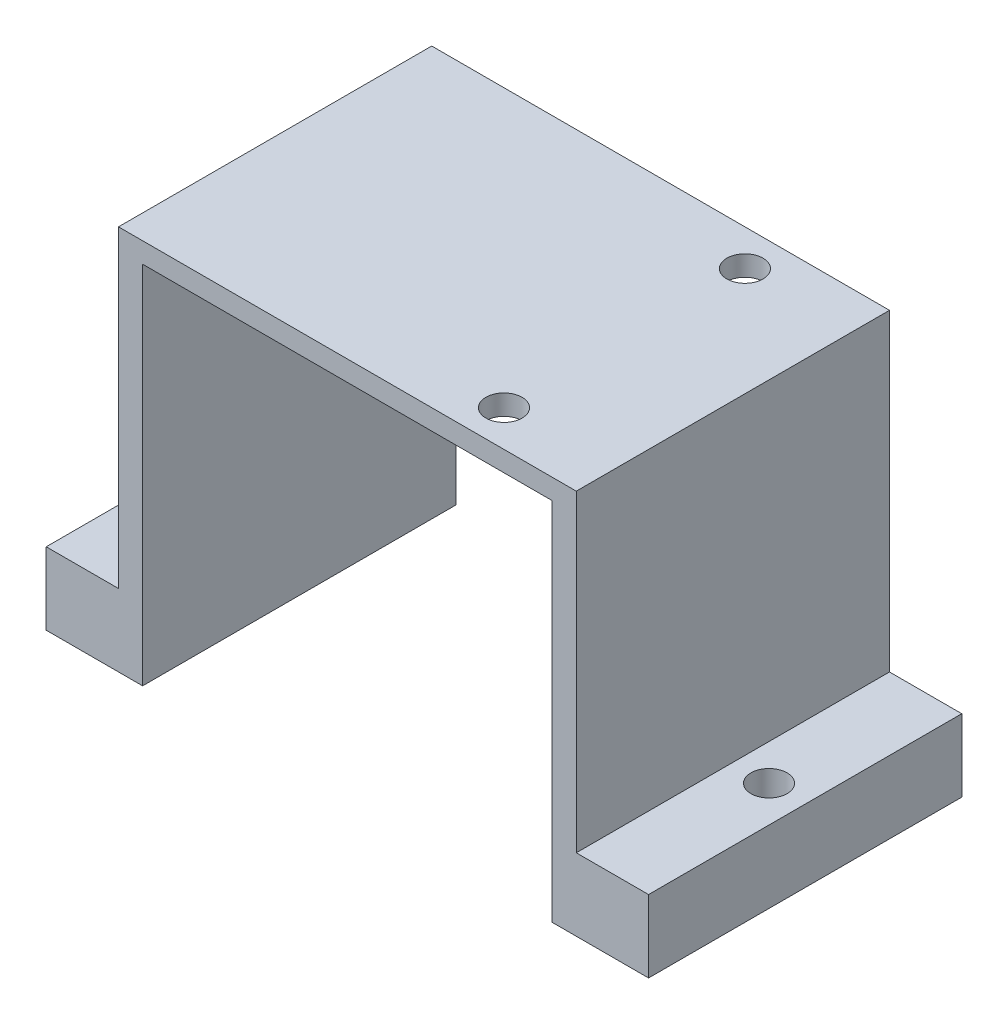
SolidWorks part; units mm, degrees
ref_plane "Front Plane" through (0, 0, 0) normal (0, 0, 1) x (1, 0, 0)
ref_plane "Top Plane" through (0, 0, 0) normal (0, 1, 0) x (1, 0, 0)
ref_plane "Right Plane" through (0, 0, 0) normal (1, 0, 0) x (0, 0, -1)
sketch "Sketch1" plane through (0, 0, 0) normal (0, 0, 1) x (1, 0, 0)
  line L0 (-19, -10) -> (-25, -10)
  line L1 (-19, -16) -> (19, -16)
  line L2 (-19, -16) -> (-19, 16)
  line L3 (-19, 16) -> (19, 16)
  line L4 (19, -16) -> (19, 16)
  line L5 (-19, -16) -> (19, 16) construction
  line L6 (-19, 16) -> (19, -16) construction
  line L7 (-25, -10) -> (-25, -16)
  line L8 (-25, -16) -> (-19, -16)
  line L9 (0, -984.5) -> (0, 49015.5) construction
  line L10 (25, -16) -> (19, -16)
  line L11 (25, -10) -> (25, -16)
  line L12 (19, -10) -> (25, -10)
  line L14 (-17, -16) -> (17, -16)
  line L15 (-17, -16) -> (-17, 14.3158)
  line L16 (-17, 14.3158) -> (17, 14.3158)
  line L17 (17, -16) -> (17, 14.3158)
  point P0 (0, 0)
  point P12 (0, 16)
  dimension "D1" = 32
  dimension "D2" = 38
  dimension "D3" = 6
  dimension "D4" = 6
  dimension "D5" = 2
  dimension "D6" = 2
extrude "Boss-Extrude1" add sketch "Sketch1" along normal blind 26 contours L7 L8 L2 L0 | L1 L4 L3 L2 | L12 L4 L10 L11 region at (-22, -13, 0) region at (-18.5032, 3, 0) region at (22, -13, 0)
sketch "Sketch2" plane through (0, 14.3158, 0) normal (0, -1, 0) x (1, 0, 0)
  line L0 (-17, 0) -> (17, 0) construction
  line L1 (-13, 0) -> (13, 0)
  line L2 (-13, 0) -> (-13, 26)
  line L3 (-13, 26) -> (13, 26)
  line L12 (13, 0) -> (13, 26)
  line L13 (-13, 0) -> (13, 26) construction
  line L14 (-13, 26) -> (13, 0) construction
  line L15 (-17, 26) -> (17, 26) construction
  line L20 (-17, 0) -> (17, 0)
  line L21 (17, 0) -> (17, 26)
  line L22 (17, 26) -> (-17, 26)
  line L23 (-17, 26) -> (-17, 0)
  line L24 (-17, 0) -> (17, 0)
  line L25 (17, 0) -> (17, 26)
  line L26 (17, 26) -> (-17, 26)
  line L27 (-17, 26) -> (-17, 0)
  circle A2 centre (10, 23) radius 1.5
  circle A3 centre (10, 3) radius 1.5
  point P4 (0, 13)
  point P17 (0, 26)
  dimension "D2" = 0
  dimension "D3" = 3
  dimension "D7" = 3
  dimension "D8" = 3
  dimension "D4" = 3
  dimension "D5" = 3
  dimension "D6" = 3
  dimension "D1" = 26
extrude "Cut-Extrude1" cut sketch "Sketch2" against normal through all contours A2 | A3 region at (10, 14.3158, 23) region at (10, 14.3158, 3)
sketch "Sketch3" plane through (0, -10, 0) normal (0, 1, 0) x (1, 0, 0)
  line L0 (0, 0) -> (0, -26) construction
  line L1 (-19, 0) -> (19, 0) construction
  line L2 (-19, -26) -> (19, -26) construction
  line L7 (25, 0) -> (19, 0)
  line L8 (19, 0) -> (19, -26)
  line L9 (19, -26) -> (25, -26)
  line L10 (25, -26) -> (25, 0)
  line L11 (25, 0) -> (19, 0)
  line L12 (19, 0) -> (19, -26)
  line L13 (19, -26) -> (25, -26)
  line L14 (25, -26) -> (25, 0)
  circle A0 centre (22, -13) radius 1.5
  circle A1 centre (-22, -13) radius 1.5
  point P12 (22, 0)
  point P13 (19, -13)
  dimension "D2" = 3
  dimension "D1" = 0
extrude "Cut-Extrude2" cut sketch "Sketch3" against normal through all contours A0 | A1 region at (22, -10, 13) region at (-22, -10, 13)
sketch "Sketch4" plane through (-19, 0, 0) normal (-1, 0, 0) x (0, 0, 1)
  line L0 (8, 11) -> (18, 11) construction
  line L1 (8, 14) -> (18, 14)
  line L2 (8, 8) -> (18, 8)
  line L4 (0, 16) -> (0, -10)
  line L5 (0, -10) -> (26, -10)
  line L6 (26, -10) -> (26, 16)
  line L7 (26, 16) -> (0, 16)
  line L8 (0, 16) -> (0, -10)
  line L9 (0, -10) -> (26, -10)
  line L10 (26, -10) -> (26, 16)
  line L11 (26, 16) -> (0, 16)
  arc A0 (8, 14) -> (8, 8) centre (8, 11) ccw
  arc A1 (18, 8) -> (18, 14) centre (18, 11) ccw
  point P6 (13, 11)
  point P11 (0, 0)
  point P12 (13, 16)
  dimension "D3" = 3
  dimension "D2" = 10
  dimension "D4" = 5
  dimension "D1" = 0
extrude "Cut-Extrude3" cut sketch "Sketch4" against normal blind 10 contours L2 A1 L1 A0 region at (-19, 11, 13)
